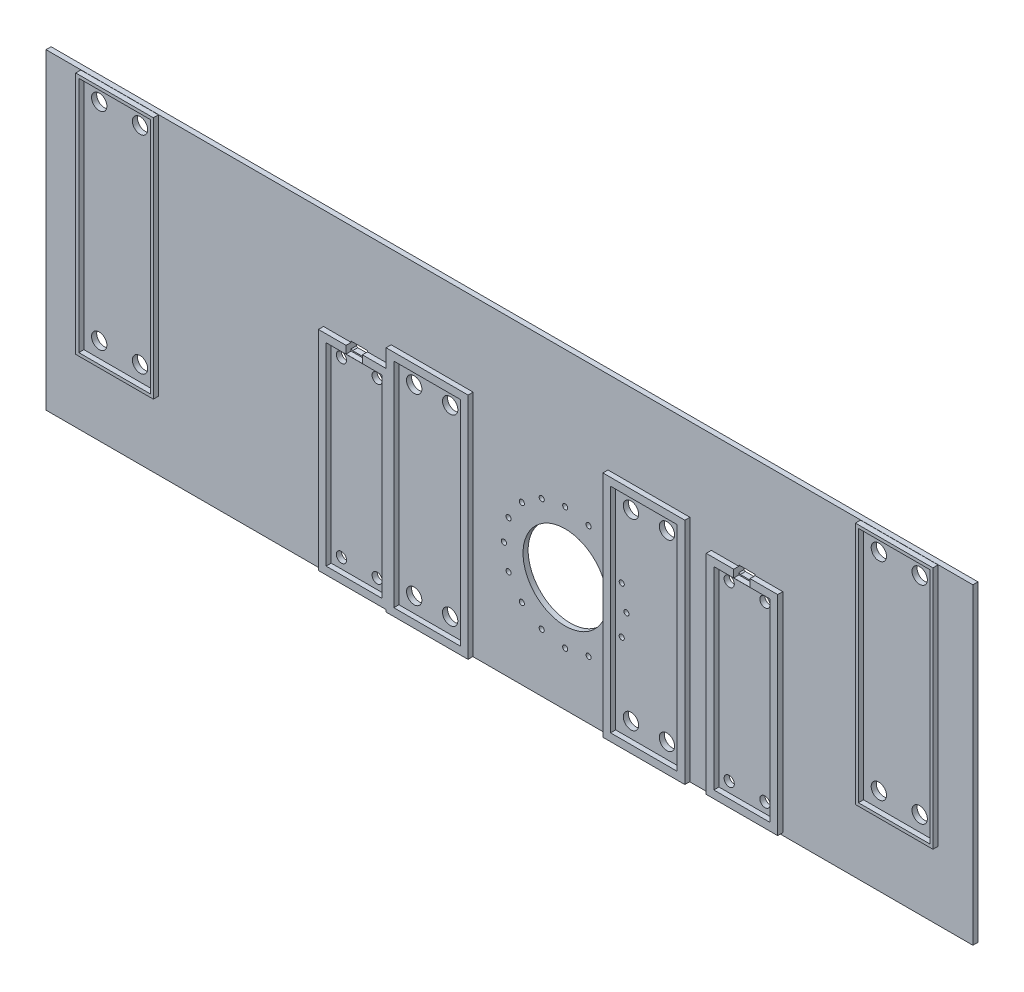
SolidWorks part; units mm, degrees
ref_plane "Front Plane" through (0, 0, 0) normal (0, 0, 1) x (1, 0, 0)
ref_plane "Top Plane" through (0, 0, 0) normal (0, 1, 0) x (1, 0, 0)
ref_plane "Right Plane" through (0, 0, 0) normal (1, 0, 0) x (0, 0, -1)
sketch "Sketch1" plane through (0, 0, 0) normal (0, 0, 1) x (1, 0, 0)
  line L1 (908, 305.83) -> (-908, 305.83)
  line L2 (908, 305.83) -> (908, -305.83)
  line L3 (908, -305.83) -> (-908, -305.83)
  line L4 (-908, 305.83) -> (-908, -305.83)
  line L5 (908, 305.83) -> (-908, -305.83) construction
  line L6 (908, -305.83) -> (-908, 305.83) construction
  point P0 (0, 0)
  dimension "D1" = 1816
  dimension "D2" = 611.66
extrude "Boss-Extrude1" add sketch "Sketch1" along normal blind 10
sketch "Sketch2" plane through (0, 0, 10) normal (0, 0, 1) x (1, 0, 0)
  line L0 (-908, -305.83) -> (908, -305.83) construction
  line L3 (0, 305.83) -> (0, -305.83) construction
  line L4 (908, 305.83) -> (-908, 305.83) construction
  line L5 (-908, -305.83) -> (908, -305.83) construction
  line L11 (-216.6367, 209.267) -> (-216.6367, -209.267)
  line L12 (54.1519, 305.83) -> (-54.1519, 305.83)
  line L24 (54.1519, 305.83) -> (54.1519, -305.83)
  line L25 (54.1519, -305.83) -> (-54.1519, -305.83)
  line L26 (-54.1519, 305.83) -> (-54.1519, -305.83)
  line L27 (54.1519, 305.83) -> (-54.1519, -305.83) construction
  line L28 (54.1519, -305.83) -> (-54.1519, 305.83) construction
  line L29 (-216.6367, 209.267) -> (-86.1659, 209.267)
  line L30 (-86.1659, 209.267) -> (-86.1659, -209.267)
  line L31 (-216.6367, -209.267) -> (-86.1659, -209.267)
  line L32 (-246.6367, 239.267) -> (-246.6367, -239.267)
  line L33 (-246.6367, 239.267) -> (-56.1659, 239.267)
  line L34 (-56.1659, 239.267) -> (-56.1659, -239.267)
  line L35 (-246.6367, -239.267) -> (-56.1659, -239.267)
  line L36 (-56.1659, 0) -> (-54.1519, 0) construction
  circle A1 centre (109.1519, -81.0465) radius 82.5
  point P12 (-151.4013, 0)
  point P13 (0, 0)
  dimension "D3" = 165
  dimension "D1" = 54.1519
  dimension "D2" = 55
  dimension "D4" = 224.7835
extrude "Cut-Extrude1" cut sketch "Sketch2" against normal through all contours L24 A1 | L24 A1 region at (117.2932, -81.0465, 10) region at (42.9779, -81.0465, 10)
sketch "Sketch3" plane through (0, 0, 10) normal (0, 0, 1) x (1, 0, 0)
  line L0 (-231.6367, -81.0465) -> (-216.6367, -81.0465) construction
  line L3 (208.0903, 128.2205) -> (338.561, 128.2205)
  line L4 (-216.6367, 128.2205) -> (-86.1659, 128.2205)
  line L5 (-216.6367, 128.2205) -> (-216.6367, -290.3135)
  line L6 (-216.6367, -290.3135) -> (-86.1659, -290.3135)
  line L7 (-86.1659, 128.2205) -> (-86.1659, -290.3135)
  line L8 (193.0903, -81.0465) -> (208.0903, -81.0465) construction
  line L9 (338.561, -81.0465) -> (353.561, -81.0465) construction
  line L10 (208.0903, 128.2205) -> (208.0903, -290.3135)
  line L11 (208.0903, -290.3135) -> (338.561, -290.3135)
  line L12 (338.561, 128.2205) -> (338.561, -290.3135)
  line L13 (-231.6367, 143.2205) -> (-71.1659, 143.2205)
  line L14 (-71.1659, 143.2205) -> (-71.1659, -305.3135)
  line L15 (-231.6367, -305.3135) -> (-71.1659, -305.3135)
  line L16 (-231.6367, 143.2205) -> (-231.6367, -305.3135)
  line L17 (193.0903, 143.2205) -> (193.0903, -305.3135)
  line L18 (193.0903, -305.3135) -> (353.561, -305.3135)
  line L19 (353.561, 143.2205) -> (353.561, -305.3135)
  line L20 (193.0903, 143.2205) -> (353.561, 143.2205)
  line L21 (-86.1659, -81.0465) -> (-71.1659, -81.0465) construction
  line L22 (-908, -305.83) -> (908, -305.83) construction
  line L23 (-216.6367, -81.0465) -> (353.561, -81.0465) construction
  point P6 (-199.8426, -14.7559)
  dimension "D1" = 130.4708
  dimension "D2" = 418.5341
  dimension "D3" = 86.1659
  dimension "D4" = 130.4708
  dimension "D5" = 418.5341
  dimension "D6" = 294.2562
  dimension "D8" = 224.7835
  dimension "D7" = 15
extrude "Boss-Extrude2" add sketch "Sketch3" along normal blind 10 contours L13 L14 L15 L16 | L17 L18 L19 L20 | L3 L12 L11 L10 | L5 L4 L7 L6
sketch "Sketch4" plane through (0, 0, 10) normal (0, 0, 1) x (1, 0, 0)
  line L0 (-186.6367, 98.2205) -> (-116.1659, -260.3135) construction
  line L1 (-908, -305.83) -> (908, -305.83) construction
  line L3 (-116.1659, 98.2205) -> (-116.1659, -260.3135)
  line L4 (238.0903, 98.2205) -> (238.0903, -260.3135)
  line L5 (-86.1659, 128.2205) -> (-86.1659, -290.3135) construction
  line L7 (-186.6367, 98.2205) -> (-186.6367, -260.3135)
  line L10 (-116.1659, 98.2205) -> (-186.6367, 98.2205)
  line L19 (238.0903, -260.3135) -> (308.561, -260.3135)
  line L26 (308.561, -260.3135) -> (308.561, 98.2205)
  line L27 (238.0903, 98.2205) -> (308.561, 98.2205)
  line L35 (-116.1659, -260.3135) -> (-186.6367, -260.3135)
  circle A8 centre (-186.6367, 98.2205) radius 15
  circle A9 centre (-116.1659, 98.2205) radius 15
  circle A10 centre (-116.1659, -260.3135) radius 15
  circle A12 centre (-186.6367, -260.3135) radius 15
  circle A13 centre (238.0903, 98.2205) radius 15
  circle A14 centre (308.561, 98.2205) radius 15
  circle A15 centre (308.561, -260.3135) radius 15
  circle A16 centre (238.0903, -260.3135) radius 15
  point P3 (-151.4013, -81.0465)
  dimension "D1" = 30
  dimension "D2" = 224.7835
  dimension "D3" = 30
extrude "Cut-Extrude2" cut sketch "Sketch4" against normal through all both and the other way through all contours L35 A10 L3 | L0 A10 L35 | L7 A12 L35 | L35 A12 L7 | L10 L0 A8 | A10 L0 L3 | A8 | A9 | A14 | A13 | A16 | A15 region at (-179.5094, 92.3578, 10) region at (-117.1333, -250.3762, 10) region at (-123.2932, -254.4507, 10) region at (-180.2705, -253.9473, 10) region at (-188.7587, -262.4356, 10) region at (-114.0439, -262.4356, 10)
sketch "Sketch5" plane through (0, 0, 0) normal (0, 0, -1) x (-1, 0, 0)
  line L0 (-908, 110.4709) -> (-370.6519, 110.4709) construction
  line L1 (-908, -305.83) -> (-908, 305.83) construction
  line L2 (908, 305.83) -> (908, -305.83) construction
  line L3 (908, 135.4709) -> (229.4029, 135.4709) construction
  line L4 (-495.6519, 305.83) -> (-495.6519, -305.83) construction
  line L5 (-908, 305.83) -> (908, 305.83) construction
  line L6 (908, -305.83) -> (-908, -305.83) construction
  line L7 (-410.6519, 305.83) -> (-410.6519, -305.83) construction
  line L8 (-370.6519, -305.83) -> (-370.6519, 110.4709) construction
  line L9 (-490.6519, 140.4709) -> (-490.6519, 105.4709)
  line L10 (-495.6519, 135.4709) -> (-505.6519, 135.4709)
  line L11 (-495.6519, 135.4709) -> (-495.6519, 110.4709)
  line L12 (-495.6519, 110.4709) -> (-505.6519, 110.4709)
  line L13 (-505.6519, 135.4709) -> (-505.6519, 110.4709)
  line L14 (-410.6519, 135.4709) -> (-400.6519, 135.4709)
  line L15 (-410.6519, 135.4709) -> (-410.6519, 110.4709)
  line L16 (-410.6519, 110.4709) -> (-400.6519, 110.4709)
  line L17 (-400.6519, 135.4709) -> (-400.6519, 110.4709)
  line L21 (-360.6519, 135.4709) -> (-360.6519, 110.4709)
  line L25 (229.4029, 135.4709) -> (229.4029, 110.4709)
  line L26 (-490.6519, 105.4709) -> (-510.6519, 105.4709)
  line L27 (-510.6519, 140.4709) -> (-510.6519, 105.4709)
  line L28 (-490.6519, 140.4709) -> (-510.6519, 140.4709)
  line L29 (-415.6519, 140.4709) -> (-415.6519, 105.4709)
  line L30 (-415.6519, 105.4709) -> (-395.6519, 105.4709)
  line L31 (-395.6519, 140.4709) -> (-395.6519, 105.4709)
  line L32 (-415.6519, 140.4709) -> (-395.6519, 140.4709)
  line L41 (-365.6519, 105.4709) -> (-345.6519, 105.4709)
  line L42 (-360.6519, 135.4709) -> (-350.6519, 135.4709)
  line L43 (-360.6519, 135.4709) -> (-360.6519, 110.4709)
  line L44 (-360.6519, 110.4709) -> (-350.6519, 110.4709)
  line L45 (-350.6519, 135.4709) -> (-350.6519, 110.4709)
  line L47 (224.4029, 140.4709) -> (244.4029, 140.4709)
  line L48 (229.4029, 135.4709) -> (239.4029, 135.4709)
  line L49 (229.4029, 135.4709) -> (229.4029, 110.4709)
  line L50 (229.4029, 110.4709) -> (239.4029, 110.4709)
  line L51 (239.4029, 135.4709) -> (239.4029, 110.4709)
  line L54 (224.4029, 105.4709) -> (244.4029, 105.4709)
  line L55 (244.4029, 105.4709) -> (244.4029, 140.4709)
  line L57 (224.4029, 105.4709) -> (224.4029, 140.4709)
  line L58 (-345.6519, 140.4709) -> (-345.6519, 105.4709)
  line L59 (-365.6519, 140.4709) -> (-365.6519, 105.4709)
  line L60 (-360.6519, 110.4709) -> (-350.6519, 110.4709) construction
  line L61 (229.4029, 110.4709) -> (908, 110.4709) construction
  line L63 (-370.6519, 135.4709) -> (-908, 135.4709) construction
  line L65 (-365.6519, 140.4709) -> (-345.6519, 140.4709)
  line L66 (-350.6519, 135.4709) -> (-360.6519, 135.4709) construction
  line L68 (-370.6519, 135.4709) -> (-370.6519, 305.83) construction
  dimension "D1" = 25
  dimension "D2" = 170.3591
  dimension "D3" = 412.3481
  dimension "D4" = 40
  dimension "D5" = 85
  dimension "D6" = 10
  dimension "D7" = 10
  dimension "D8" = 10
  dimension "D9" = 5
  dimension "D10" = 5
  dimension "D12" = 10
  dimension "D13" = 10
  dimension "D14" = 5
  dimension "D15" = 5
  dimension "D11" = 5
extrude "Boss-Extrude3" add sketch "Sketch5" along normal blind 5 contours L9 L28 L27 L26 L13 L10 L11 L12 | L32 L29 L30 L31 L14 L17 L16 L15 | L65 L59 L41 L58 L42 L45 L44 L21 | L57 L54 L55 L47 L48 L51 L50 L25 region at (491.055, 122.9709, 0) region at (405.6519, 140.0678, 0) region at (365.2488, 122.9709, 0) region at (-234.4029, 140.0678, 0)
sketch "Sketch6" plane through (0, 0, 10) normal (0, 0, 1) x (1, 0, 0)
  line L0 (520.5256, -286.0465) -> (395.5256, -286.0465) construction
  line L1 (410.5256, 93.0245) -> (520.5256, 93.0245)
  line L2 (410.5256, 93.0245) -> (410.5256, -286.0465)
  line L3 (410.5256, -286.0465) -> (520.5256, -286.0465)
  line L4 (520.5256, 93.0245) -> (520.5256, -286.0465)
  line L5 (208.0903, -290.3135) -> (338.561, -290.3135) construction
  line L6 (-216.6367, 128.2205) -> (-216.6367, -290.3135) construction
  line L7 (338.561, 128.2205) -> (338.561, -290.3135) construction
  line L8 (-364.2201, 108.0245) -> (-364.2201, -301.0465)
  line L9 (-349.2201, 93.0245) -> (-239.2201, 93.0245)
  line L10 (-349.2201, 93.0245) -> (-349.2201, -286.0465)
  line L11 (-349.2201, -286.0465) -> (-239.2201, -286.0465)
  line L12 (-239.2201, 93.0245) -> (-239.2201, -286.0465)
  line L13 (-364.2201, -301.0465) -> (-231.6367, -301.0465)
  line L15 (-364.2201, 108.0245) -> (-231.6367, 108.0245)
  line L16 (395.5256, 108.0245) -> (395.5256, -301.0465)
  line L17 (395.5256, -301.0465) -> (535.5256, -301.0465)
  line L18 (535.5256, 108.0245) -> (535.5256, -301.0465)
  line L19 (395.5256, 108.0245) -> (535.5256, 108.0245)
  line L20 (-224.2201, 108.0245) -> (-224.2201, -301.0465) construction
  line L21 (-231.6367, 108.0245) -> (-231.6367, -301.0465)
  line L22 (-231.6367, 143.2205) -> (-231.6367, -305.3135) construction
  line L23 (-231.6367, -286.0465) -> (-596.1227, -286.0465) construction
  line L24 (-364.2201, -301.0465) -> (-224.2201, -301.0465) construction
  line L25 (-364.2201, 108.0245) -> (-224.2201, 108.0245) construction
  point P4 (465.5256, -286.0465)
  dimension "D1" = 110
  dimension "D2" = 379.071
  dimension "D3" = 4.267
  dimension "D4" = 71.9646
  dimension "D5" = 110
  dimension "D6" = 379.071
  dimension "D7" = 22.5834
  dimension "D8" = 15
extrude "Boss-Extrude4" add sketch "Sketch6" along normal blind 10
sketch "Sketch7" plane through (0, 0, 0) normal (0, 0, -1) x (-1, 0, 0)
  line L0 (186.6367, 98.2205) -> (278.1379, 98.2205)
  line L1 (-308.561, 98.2205) -> (-449.4429, 98.2205)
  line L2 (-449.4429, 98.2205) -> (-449.4429, 93.2205)
  line L3 (-449.4429, 93.2205) -> (-481.4429, 93.2205)
  line L4 (-449.4429, 98.2205) -> (-449.4429, 110.2205)
  line L5 (-449.4429, 110.2205) -> (-481.4429, 110.2205)
  line L6 (-465.4429, 110.2205) -> (-465.4429, 68.9883) construction
  line L7 (-481.4429, 98.2205) -> (-481.4429, 110.2205)
  line L8 (-481.4429, 98.2205) -> (-481.4429, 93.2205)
  line L9 (278.1379, 98.2205) -> (278.1379, 110.2205)
  line L10 (278.1379, 110.2205) -> (310.1379, 110.2205)
  line L11 (278.1379, 98.2205) -> (278.1379, 93.2205)
  line L12 (278.1379, 93.2205) -> (310.1379, 93.2205)
  line L13 (294.1379, 110.2205) -> (294.1379, 41.4699) construction
  line L14 (310.1379, 98.2205) -> (310.1379, 93.2205)
  line L15 (310.1379, 98.2205) -> (310.1379, 110.2205)
  point P14 (-465.4429, 93.2205)
  point P20 (294.1379, 93.2205)
  dimension "D1" = 140.8819
  dimension "D2" = 91.5012
  dimension "D3" = 12
  dimension "D4" = 5
  dimension "D5" = 16
  dimension "D6" = 5
  dimension "D7" = 12
  dimension "D8" = 16
extrude "Cut-Extrude3" cut sketch "Sketch7" against normal through all contours L14 L15 L10 L9 L11 L12 | L7 L8 L3 L2 L4 L5 region at (465.4429, 101.7205, 0) region at (-294.1379, 101.7205, 0)
sketch "Sketch8" plane through (0, 0, 0) normal (0, 0, -1) x (-1, 0, 0)
  line L0 (278.1379, 93.2205) -> (310.1379, 93.2205) construction
  line L1 (281.0908, 95.5245) -> (307.185, 95.5245)
  line L2 (281.0908, 95.5245) -> (278.1379, 97.2581)
  line L3 (278.1379, 93.2205) -> (278.1379, 110.2205) construction
  line L4 (278.1379, 97.2581) -> (278.1379, 93.2205)
  line L5 (278.1379, 93.2205) -> (310.1379, 93.2205)
  line L6 (310.1379, 93.2205) -> (310.1379, 97.2581)
  line L7 (310.1379, 110.2205) -> (310.1379, 93.2205) construction
  line L8 (310.1379, 97.2581) -> (307.185, 95.5245)
  point P6 (294.1379, 95.5245)
  point P7 (294.1379, 93.2205)
  dimension "D1" = 26.0941
  dimension "D2" = 2.304
extrude "Boss-Extrude5" add sketch "Sketch8" against normal up to surface (10 mm away) up to face at (465.4843, 6.3058, 10)
sketch "Sketch9" plane through (0, 0, 0) normal (0, 0, -1) x (-1, 0, 0)
  line L0 (-478.49, 95.5245) -> (-452.3958, 95.5245)
  line L1 (-449.4429, 93.2205) -> (-481.4429, 93.2205) construction
  line L2 (-481.4429, 93.2205) -> (-449.4429, 93.2205)
  line L4 (-452.3958, 95.5245) -> (-449.4429, 97.2581)
  line L5 (-478.49, 95.5245) -> (-481.4429, 97.2581)
  line L6 (-481.4429, 97.2581) -> (-481.4429, 93.2205)
  line L7 (-449.4429, 93.2205) -> (-449.4429, 97.2581)
  point P8 (-465.4429, 93.2205)
  point P9 (-465.4429, 95.5245)
  dimension "D1" = 26.0941
  dimension "D2" = 2.304
extrude "Boss-Extrude6" add sketch "Sketch9" against normal up to surface (10 mm away) up to face at (465.4843, 6.3058, 10)
sketch "Sketch10" plane through (0, 0, 10) normal (0, 0, 1) x (1, 0, 0)
  line L0 (-908, 305.83) -> (-908, -305.83) construction
  line L1 (-833.7168, 299.4172) -> (-693.7168, 299.4172)
  line L2 (-833.7168, 299.4172) -> (-833.7168, -166.0465)
  line L3 (-833.7168, -166.0465) -> (-693.7168, -166.0465)
  line L4 (-693.7168, 299.4172) -> (-693.7168, -166.0465)
  line L5 (693.7168, 299.4172) -> (833.7168, 299.4172)
  line L6 (693.7168, 299.4172) -> (693.7168, -166.0465)
  line L7 (693.7168, -166.0465) -> (833.7168, -166.0465)
  line L8 (833.7168, 299.4172) -> (833.7168, -166.0465)
  line L9 (908, 305.83) -> (-908, 305.83) construction
  line L10 (687.7168, 305.4172) -> (687.7168, -172.0465)
  line L11 (687.7168, -172.0465) -> (839.7168, -172.0465)
  line L12 (839.7168, 305.4172) -> (839.7168, -172.0465)
  line L13 (687.7168, 305.4172) -> (839.7168, 305.4172)
  line L14 (-839.7168, 305.4172) -> (-839.7168, -172.0465)
  line L15 (-839.7168, -172.0465) -> (-687.7168, -172.0465)
  line L16 (-687.7168, 305.4172) -> (-687.7168, -172.0465)
  line L17 (-839.7168, 305.4172) -> (-687.7168, 305.4172)
  line L18 (908, -305.83) -> (908, 305.83) construction
  dimension "D1" = 140
  dimension "D2" = 140
  dimension "D3" = 465.4637
  dimension "D4" = 74.2832
  dimension "D5" = 6.4128
  dimension "D7" = 74.2832
  dimension "D6" = 6
extrude "Boss-Extrude7" add sketch "Sketch10" along normal blind 10
sketch "Sketch11" plane through (0, 0, 10) normal (0, 0, 1) x (1, 0, 0)
  line L12 (-259.2201, 73.0245) -> (-329.2201, 73.0245)
  line L13 (-329.2201, 73.0245) -> (-329.2201, -266.0465)
  line L14 (-329.2201, -266.0465) -> (-259.2201, -266.0465)
  line L15 (-259.2201, -266.0465) -> (-259.2201, 73.0245)
  line L16 (-269.2201, 73.0245) -> (-319.2201, 73.0245)
  line L17 (-329.2201, 63.0245) -> (-329.2201, -256.0465)
  line L18 (-319.2201, -266.0465) -> (-269.2201, -266.0465)
  line L19 (-259.2201, -256.0465) -> (-259.2201, 63.0245)
  circle A0 centre (-329.2201, 73.0245) radius 10
  circle A1 centre (-259.2201, 73.0245) radius 10
  circle A2 centre (-259.2201, -266.0465) radius 10
  circle A3 centre (-329.2201, -266.0465) radius 10
  dimension "D2" = 20
  dimension "D3" = 20
  dimension "D4" = 20
  dimension "D5" = 20
  dimension "D1" = 20
extrude "Cut-Extrude4" cut sketch "Sketch11" against normal through all contours A2 | A3 | A1 | A0
sketch "Sketch12" plane through (0, 0, 10) normal (0, 0, 1) x (1, 0, 0)
  line L8 (500.5256, 73.0245) -> (430.5256, 73.0245)
  line L9 (430.5256, 73.0245) -> (430.5256, -266.0465)
  line L10 (430.5256, -266.0465) -> (500.5256, -266.0465)
  line L11 (500.5256, -266.0465) -> (500.5256, 73.0245)
  line L12 (490.5256, 73.0245) -> (440.5256, 73.0245)
  line L13 (430.5256, 63.0245) -> (430.5256, -256.0465)
  line L14 (440.5256, -266.0465) -> (490.5256, -266.0465)
  line L15 (500.5256, -256.0465) -> (500.5256, 63.0245)
  circle A0 centre (430.5256, 73.0245) radius 10
  circle A1 centre (500.5256, 73.0245) radius 10
  circle A2 centre (500.5256, -266.0465) radius 10
  circle A3 centre (430.5256, -266.0465) radius 10
  dimension "D2" = 20
  dimension "D3" = 20
  dimension "D4" = 20
  dimension "D5" = 20
  dimension "D1" = 20
extrude "Cut-Extrude5" cut sketch "Sketch12" against normal through all contours A0 | A1 | A2 | A3
sketch "Sketch13" plane through (0, 0, 10) normal (0, 0, 1) x (1, 0, 0)
  line L8 (803.7168, 269.4172) -> (723.7168, 269.4172)
  line L9 (723.7168, 269.4172) -> (723.7168, -136.0465)
  line L10 (723.7168, -136.0465) -> (803.7168, -136.0465)
  line L11 (803.7168, -136.0465) -> (803.7168, 269.4172)
  line L12 (788.7168, 269.4172) -> (738.7168, 269.4172)
  line L13 (723.7168, 254.4172) -> (723.7168, -121.0465)
  line L14 (738.7168, -136.0465) -> (788.7168, -136.0465)
  line L15 (803.7168, -121.0465) -> (803.7168, 254.4172)
  line L20 (-723.7168, 269.4172) -> (-803.7168, 269.4172)
  line L21 (-803.7168, 269.4172) -> (-803.7168, -136.0465)
  line L22 (-803.7168, -136.0465) -> (-723.7168, -136.0465)
  line L23 (-723.7168, -136.0465) -> (-723.7168, 269.4172)
  line L24 (-738.7168, 269.4172) -> (-788.7168, 269.4172)
  line L25 (-803.7168, 254.4172) -> (-803.7168, -121.0465)
  line L26 (-788.7168, -136.0465) -> (-738.7168, -136.0465)
  line L27 (-723.7168, -121.0465) -> (-723.7168, 254.4172)
  circle A0 centre (-723.7168, -136.0465) radius 15
  circle A1 centre (-803.7168, -136.0465) radius 15
  circle A2 centre (-723.7168, 269.4172) radius 15
  circle A3 centre (-803.7168, 269.4172) radius 15
  circle A4 centre (803.7168, -136.0465) radius 15
  circle A5 centre (723.7168, -136.0465) radius 15
  circle A6 centre (723.7168, 269.4172) radius 15
  circle A7 centre (803.7168, 269.4172) radius 15
  dimension "D3" = 30
  dimension "D1" = 30
  dimension "D2" = 30
extrude "Cut-Extrude6" cut sketch "Sketch13" against normal through all contours A6 | A7 | A4 | A5 | A0 | A1 | A3 | A2
sketch "Sketch14" plane through (0, 0, 0) normal (0, 0, -1) x (-1, 0, 0)
  circle A0 centre (-109.1519, -81.0465) radius 120 construction
  circle A1 centre (-109.1519, 38.9535) radius 5
  circle A2 centre (-63.2299, 29.8191) radius 5
  circle A3 centre (-24.2991, 3.8063) radius 5
  circle A4 centre (1.7136, -35.1245) radius 5
  circle A5 centre (10.8481, -81.0465) radius 5
  circle A6 centre (1.7136, -126.9685) radius 5
  circle A7 centre (-24.2991, -165.8993) radius 5
  circle A8 centre (-63.2299, -191.912) radius 5
  circle A9 centre (-109.1519, -201.0465) radius 5
  circle A10 centre (-155.0739, -191.912) radius 5
  circle A11 centre (-194.0047, -165.8993) radius 5
  circle A12 centre (-220.0174, -126.9685) radius 5
  circle A13 centre (-229.1519, -81.0465) radius 5
  circle A14 centre (-220.0174, -35.1245) radius 5
  circle A15 centre (-194.0047, 3.8063) radius 5
  circle A16 centre (-155.0739, 29.8191) radius 5
  point P38 (-109.1519, -81.0465)
  dimension "D1" = 240
  dimension "D2" = 10
  dimension "D3" = 16
extrude "Cut-Extrude7" cut sketch "Sketch14" against normal blind 10
